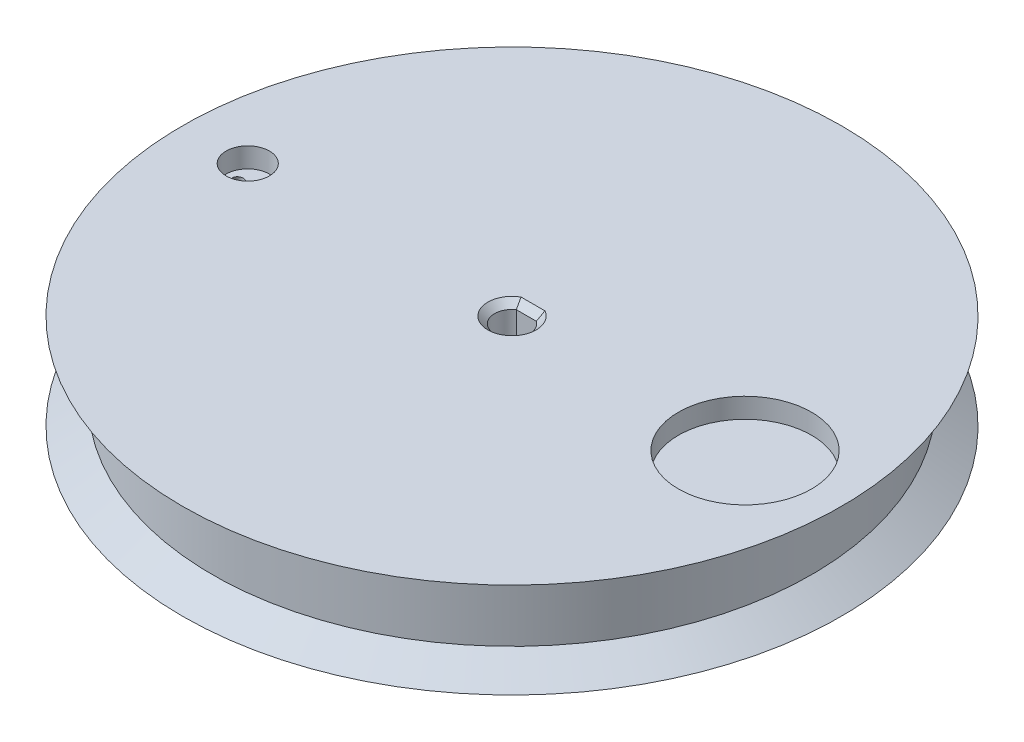
SolidWorks part; units mm, degrees
ref_plane "Front Plane" through (0, 0, 0) normal (0, 0, 1) x (1, 0, 0)
ref_plane "Top Plane" through (0, 0, 0) normal (0, 1, 0) x (1, 0, 0)
ref_plane "Right Plane" through (0, 0, 0) normal (1, 0, 0) x (0, 0, -1)
sketch "Sketch2" plane through (0, 0, 0) normal (0, 0, 1) x (1, 0, 0)
  line L0 (0, 0) -> (0, 59.7538) construction
  line L1 (0, 0) -> (-49.4987, 0)
  line L2 (-49.4987, 14.3) -> (-45, 11.15)
  line L3 (-49.4987, 14.3) -> (0, 14.3)
  line L4 (-45, 11.15) -> (-45, 3.15)
  line L5 (-45, 3.15) -> (-49.4987, 0)
  line L6 (0, 0) -> (0, 14.3)
  line L7 (0, 14.3) -> (0, 0)
  dimension "D4" = 8
  dimension "D1" = 35
  dimension "D2" = 14.3
  dimension "D3" = 45
  dimension "D5" = 49.4987
revolve "Revolve1" add sketch "Sketch2" angle 360 about L0 region at (-23.0171, 7.15, 0)
sketch "Sketch4" plane through (0, 14.3, 0) normal (0, 1, 0) x (1, 0, 0)
  line L0 (1.506, 2.15) -> (-1.506, 2.15)
  arc A0 (-1.506, 2.15) -> (1.506, 2.15) centre (0, 0) ccw
  dimension "D1" = 5.25
  dimension "D2" = 2.15
extrude "Cut-Extrude2" cut sketch "Sketch4" against normal blind 27
chamfer "Chamfer2" distance 1 angle 45 4 edges at (0, 14.3, -2.15) (0, 14.3, 2.625) (0, 0, -2.15) (0, 0, 2.625)
sketch "Sketch9" plane through (0, 0, 0) normal (0, 0, 1) x (1, 0, 0)
  line L1 (-45, 3.15) -> (-45, 11.15) construction
  spline S0 degree 3 poles (-51.8051, 7.7042) (-45.1514, 3.2919) (-39.6338, 11.0867) (-39.7167, 16.7061) knots 0 0 0 0 1 1 1 1
sweep "Cut-Sweep1" cut path "Sketch9" circular profile diameter 1.5 parameters "D3"=1.5
sketch "Sketch24" plane through (0, 14.3, 0) normal (0, 1, 0) x (1, 0, 0)
  circle A0 centre (-39.6881, 0) radius 3.2486
extrude "Cut-Extrude7" cut sketch "Sketch24" against normal blind 3
sketch "Sketch32" plane through (0, 14.3, 0) normal (0, 1, 0) x (1, 0, 0)
  circle A0 centre (35, 0) radius 10
  point P2 (0, 0)
  point P4 (33.1393, 0)
  dimension "D1" = 20
  dimension "D2" = 35
extrude "Cut-Extrude9" cut sketch "Sketch32" against normal blind 3
sketch "Sketch33" plane through (0, 0, -2.15) normal (0, 0, 1) x (1, 0, 0)
  line L0 (1.506, 13.3) -> (-1.506, 1) construction
  circle A0 centre (0, 7.15) radius 1.85
  dimension "D1" = 3.7
extrude "Cut-Extrude10" cut sketch "Sketch33" against normal blind 26
sketch "Sketch34" plane through (0, 0, -28.15) normal (0, 0, 1) x (1, 0, 0)
  circle A0 centre (0, 7.15) radius 3.65
  dimension "D1" = 7.3
extrude "Cut-Extrude11" cut sketch "Sketch34" against normal blind 26
sketch "Sketch26" plane through (0, 14.3, 0) normal (0, 1, 0) x (1, 0, 0)
  circle A0 centre (0, 0) radius 30 construction
  circle A1 centre (0, 0) radius 34
  circle A2 centre (0, 0) radius 11.2502
  dimension "60" = 60
  dimension "D2" = 4
extrude "Cut-Extrude13" cut sketch "Sketch26" along normal blind 3 from surface starting at face at (0, 0, 0.2375)
fillet "Fillet1" radius 1.5 4 edges at (0, 0, -34) (0, 3, -34) (0, 3, -11.2502) (0, 0, -11.2502)
